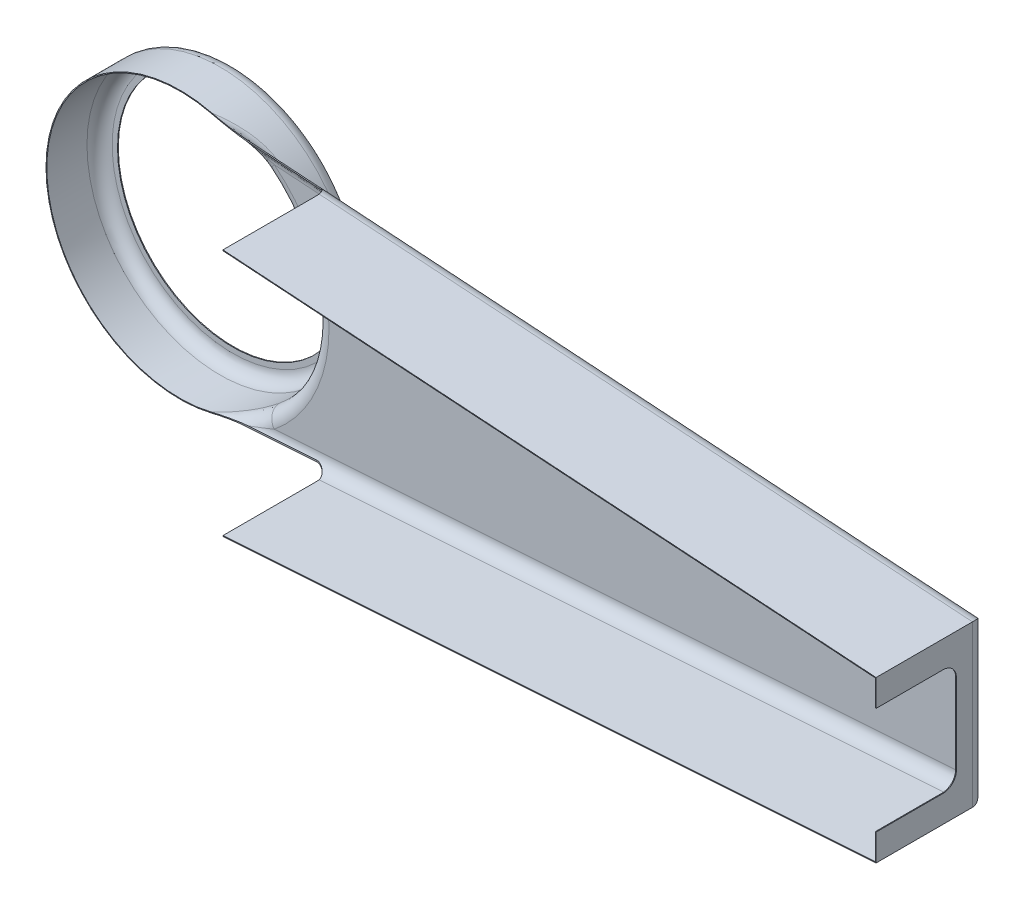
SolidWorks part; units mm, degrees
note: The reader was unsure of these and kept them because the rebuilt part matched: shared geometry of "Sketch1<3>".
ref_plane "Front Plane" through (0, 0, 0) normal (0, 0, 1) x (1, 0, 0)
ref_plane "Top Plane" through (0, 0, 0) normal (0, 1, 0) x (1, 0, 0)
ref_plane "Right Plane" through (0, 0, 0) normal (1, 0, 0) x (0, 0, -1)
sketch "Sketch1" plane through (0, 0, 0) normal (0, 0, 1) x (1, 0, 0)
  line L0 (0, 0) -> (415.6133, 0) construction
  line L1 (300, 78.5838) -> (300, -93.4876) construction
  line L2 (300, 30) -> (3.3445, 49.888)
  line L4 (300, 30) -> (300, -30)
  line L5 (300, -30) -> (3.3445, -49.888)
  circle A0 centre (0, 0) radius 50
  circle A1 centre (0, 0) radius 43
  point P0 (0, 0)
  point P4 (300, 0)
  point P8 (300, 30)
  point P9 (300, -30)
  dimension "D1" = 100
  dimension "D5" = 86
  dimension "D2" = 300
  dimension "D3" = 30
  dimension "D4" = 30
extrude "Boss-Extrude1" add sketch "Sketch1" against normal blind 60 contours A0 A1
extrude "Boss-Extrude2" add sketch "Sketch1<3>" against normal blind 41 contours A0 L5 L4 L2
sketch "Sketch1<3>" plane through (0, 0, 0) normal (0, 0, 1) x (1, 0, 0) same geometry as "Sketch1"
fillet "Fillet1" radius 5 5 edges at (50, 0, -41) (50, 0, -60) (151.6723, -39.944, -41) (300, 0, -41) (151.6723, 39.944, -41)
shell "Shell2" thickness 0.3
ref_plane "Plane1" through (300, 0, 0) normal (1, 0, 0) x (0, 0, -1)
sketch "Sketch2" plane through (300, 0, 0) normal (1, 0, 0) x (0, 0, -1)
  line L1 (-30, 20) -> (30, 20)
  line L2 (-30, 20) -> (-30, -20)
  line L3 (-30, -20) -> (30, -20)
  line L4 (30, 20) -> (30, -20)
  line L5 (-30, 20) -> (30, -20) construction
  line L6 (-30, -20) -> (30, 20) construction
  point P0 (0, 0)
  dimension "D1" = 40
  dimension "D2" = 60
extrude "Cut-Extrude1" cut sketch "Sketch2" against normal blind 40
fillet "Fillet2" radius 5 2 edges at (299.85, -20, -30) (299.85, 20, -30)
sketch "Sketch3" plane through (0, 0, 0) normal (0, 0, 1) x (1, 0, 0)
  line L1 (-56.0747, 63.3263) -> (56.0747, 63.3263)
  line L2 (-56.0747, 63.3263) -> (-56.0747, -63.3263)
  line L3 (-56.0747, -63.3263) -> (56.0747, -63.3263)
  line L4 (56.0747, 63.3263) -> (56.0747, -63.3263)
  line L5 (-56.0747, 63.3263) -> (56.0747, -63.3263) construction
  line L6 (-56.0747, -63.3263) -> (56.0747, 63.3263) construction
  point P0 (0, 0)
extrude "Cut-Extrude2" cut sketch "Sketch3" against normal blind 40
fillet "Fillet3" radius 5 2 edges at (56.0747, -44.0818, -40) (56.0747, 44.0818, -40)
